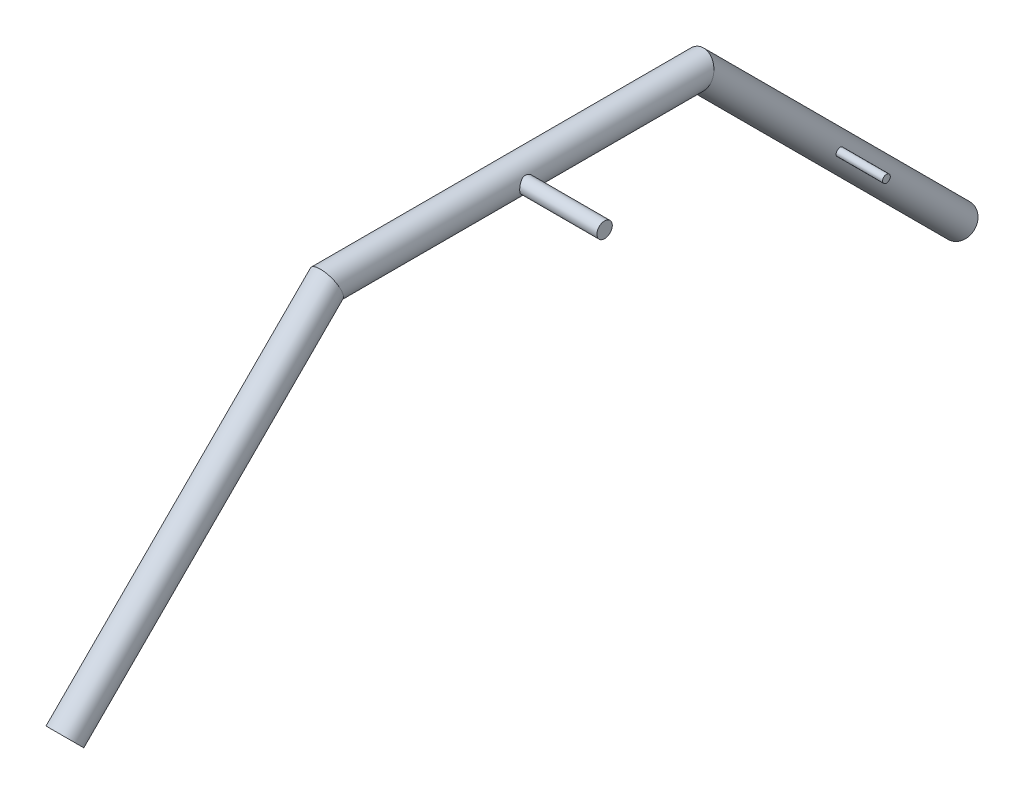
SolidWorks part; units mm, degrees
material "6061 Alloy"
ref_plane "Front Plane" through (0, 0, 0) normal (0, 0, 1) x (1, 0, 0)
ref_plane "Top Plane" through (0, 0, 0) normal (0, 1, 0) x (1, 0, 0)
ref_plane "Right Plane" through (0, 0, 0) normal (1, 0, 0) x (0, 0, -1)
sketch "Sketch2" plane through (0, 0, 0) normal (1, 0, 0) x (0, 0, -1)
  line L0 (-248.1823, -217.0159) -> (-32.6561, -1.4898)
  line L1 (-32.6561, -1.4898) -> (272.1439, -1.4898)
  line L2 (272.1439, -1.4898) -> (487.67, -217.0159)
  dimension "D1" = 135
  dimension "D2" = 135
  dimension "D3" = 304.8
  dimension "D4" = 304.8
  dimension "D5" = 304.8
sweep "Sweep1" add path "Sketch2" circular profile diameter 25.4 parameters "D3"=25.4
sweep "Cut-Sweep1" cut path "Sketch2<2>" circular profile diameter 19.05 parameters "D3"=19.05
sketch "Sketch2<2>" plane through (0, 0, 0) normal (1, 0, 0) x (0, 0, -1) same geometry as "Sketch2"
sketch "Sketch19" plane through (0, 0, 0) normal (1, 0, 0) x (0, 0, -1)
  line L0 (266.8834, -14.1898) -> (266.8834, 11.2102) construction
  line L1 (277.4044, 11.2102) -> (-37.9166, 11.2102) construction
  line L2 (266.8834, 11.2102) -> (-27.3956, -14.1898) construction
  line L3 (-27.3956, -14.1898) -> (-27.3956, 11.2102) construction
  line L4 (-27.3956, 11.2102) -> (266.8834, -14.1898) construction
  circle A0 centre (119.7439, -1.4898) radius 6.35
  dimension "D1" = 12.7
extrude "Boss-Extrude1" add sketch "Sketch19" along normal blind 76.2
sketch "Sketch28" plane through (0, 0, 0) normal (1, 0, 0) x (0, 0, -1)
  line L0 (272.1439, -1.4898) -> (487.67, -217.0159) construction
  line L1 (277.4044, 11.2102) -> (266.8834, -14.1898) construction
  line L2 (478.6898, -225.9962) -> (496.6503, -208.0357) construction
  circle A0 centre (377.0898, -106.4357) radius 3.175
  point P0 (478.6898, -225.9962)
  dimension "D2" = 6.35
  dimension "D1" = 101.6
extrude "Boss-Extrude2" add sketch "Sketch28" along normal blind 50.8
equation "\"D2@Sketch2\"=\"D1@Sketch2\""
equation "\"D5@Sketch2\"=\"D4@Sketch2\""
